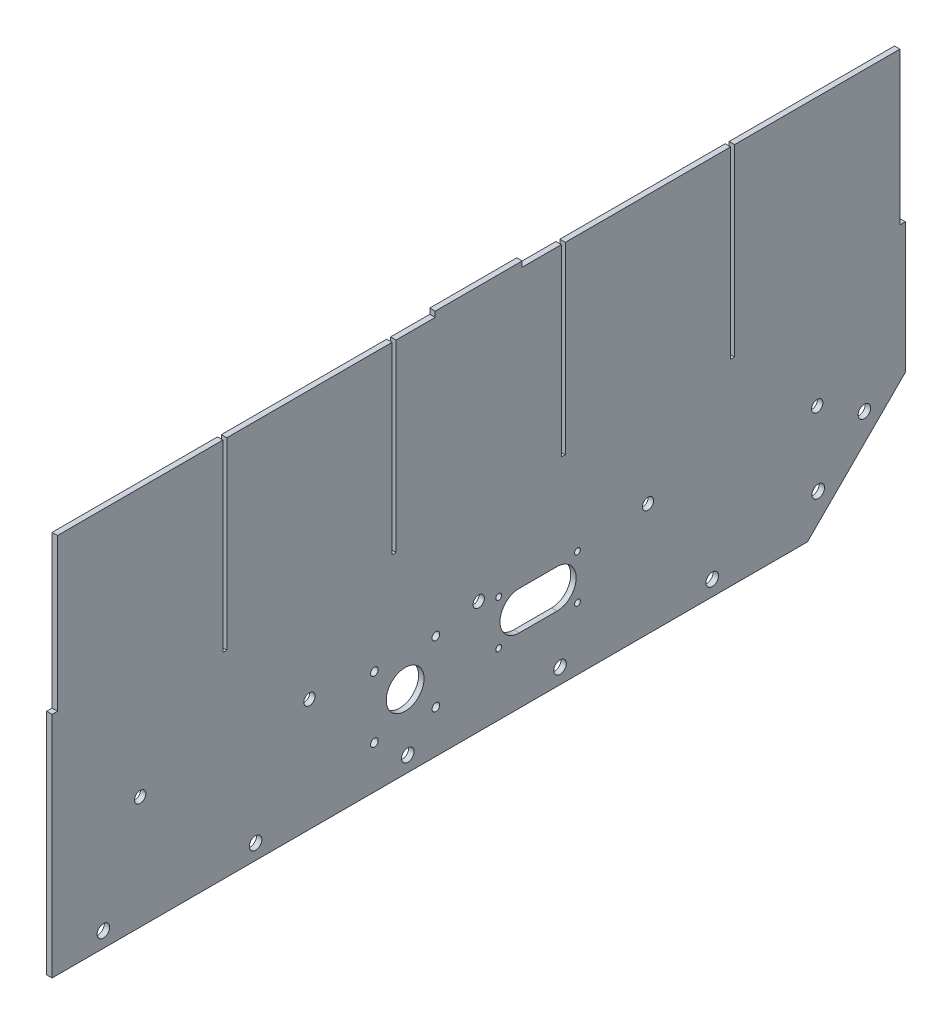
SolidWorks part; units mm, degrees
material "6061-T6 (SS)"
ref_plane "X-Y Datum" through (0, 0, 0) normal (0, 0, 1) x (1, 0, 0)
ref_plane "X-Z Datum" through (0, 0, 0) normal (0, 1, 0) x (1, 0, 0)
ref_plane "Y-Z Datum" through (0, 0, 0) normal (1, 0, 0) x (0, 0, -1)
sketch "Sketch1" plane through (0, 0, 0) normal (1, 0, 0) x (0, 0, -1)
  line L1 (-249.174, 82.55) -> (249.174, 82.55)
  line L2 (-249.174, 82.55) -> (-249.174, -82.55)
  line L3 (-249.174, -82.55) -> (249.174, -82.55)
  line L4 (249.174, 82.55) -> (249.174, -82.55)
  line L5 (-249.174, 82.55) -> (249.174, -82.55) construction
  line L6 (-249.174, -82.55) -> (249.174, 82.55) construction
  point P0 (0, 0)
  dimension "D1" = 165.1
  dimension "D2" = 498.348
extrude "Boss-Extrude1" add sketch "Sketch1" along normal mid plane 3.175
sketch "Sketch2" plane through (1.5875, 0, 0) normal (1, 0, 0) x (0, 0, -1)
  line L2 (249.174, -82.55) -> (192.024, -139.7)
  line L5 (-249.174, -82.55) -> (249.174, -82.55) construction
  line L6 (-249.174, -82.55) -> (249.174, -82.55)
  line L8 (192.024, -139.7) -> (-249.174, -139.7)
  line L9 (-249.174, -139.7) -> (-249.174, -82.55)
  line L11 (-249.174, 82.55) -> (-249.174, -82.55) construction
  line L12 (249.174, -82.55) -> (249.174, 82.55) construction
  line M10 (-249.174, -82.55) -> (249.174, -82.55)
  dimension "D1" = 45
  dimension "D5" = 57.15
extrude "Boss-Extrude2" add sketch "Sketch2" against normal blind 3.175 contours L2 M10 region at (1.5875, -110.5456, 13.9978)
sketch "Sketch3" plane through (-1.5875, 0, 0) normal (-1, 0, 0) x (0, 0, 1)
  line L0 (219.202, -139.7) -> (219.202, -130.81)
  line L1 (-192.024, -139.7) -> (249.174, -139.7) construction
  line L2 (219.202, -130.81) -> (249.174, -130.81)
  line L3 (249.174, 82.55) -> (249.174, -139.7) construction
  circle A0 centre (219.202, -130.81) radius 3.675
  dimension "D1" = 7.35
extrude "Cut-Extrude1" cut sketch "Sketch3" against normal through all contours L0 A0 L2 | L2 A0 L0 region at (-1.5875, -130.2901, 218.6821) region at (-1.5875, -132.3697, 220.7617)
pattern_linear "LPattern1" count 5 spacing 88.9 along (0, 0, -1) of "Cut-Extrude1"
sketch "Sketch4" plane through (-1.5875, 0, 0) normal (-1, 0, 0) x (0, 0, 1)
  line L0 (-206.3924, -125.3316) -> (-198.3102, -117.2494)
  line L1 (-249.174, -82.55) -> (-192.024, -139.7) construction
  line L2 (-192.024, -139.7) -> (-183.9418, -131.6178)
  line L3 (-183.9418, -131.6178) -> (-198.3102, -117.2494)
  circle A0 centre (-198.3102, -117.2494) radius 3.675
extrude "Cut-Extrude2" cut sketch "Sketch4" against normal through all and the other way through all contours L3 A0 L0 | L0 A0 L3 region at (-1.5875, -116.5141, -198.3102) region at (-1.5875, -119.4551, -198.3102)
pattern_linear "LPattern2" count 2 spacing 38.1 along (0, 0.7071, -0.7071) of "Cut-Extrude2"
sketch "Sketch5" plane through (1.5875, 0, 0) normal (1, 0, 0) x (0, 0, -1)
  line L1 (249.174, 82.55) -> (245.999, 82.55)
  line L2 (249.174, 82.55) -> (249.174, -6.35)
  line L3 (249.174, -6.35) -> (245.999, -6.35)
  line L4 (245.999, 82.55) -> (245.999, -6.35)
  line L5 (-249.174, 82.55) -> (-245.999, 82.55)
  line L6 (-249.174, 82.55) -> (-249.174, -6.35)
  line L7 (-249.174, -6.35) -> (-245.999, -6.35)
  line L8 (-245.999, 82.55) -> (-245.999, -6.35)
  dimension "D1" = 3.175
  dimension "D2" = 88.9
  dimension "D3" = 3.175
  dimension "D4" = 88.9
extrude "Cut-Extrude3" cut sketch "Sketch5" against normal through all
sketch "Sketch6" plane through (1.5875, 0, 0) normal (1, 0, 0) x (0, 0, -1)
  line L1 (149.4282, -24.892) -> (149.4282, 82.55) construction
  line L2 (122.174, 82.55) -> (249.174, 82.55)
  line L3 (149.4282, -24.892) -> (149.4282, 82.55)
  line L5 (149.4282, 82.55) -> (147.1422, 82.55)
  line L6 (149.4282, 82.55) -> (149.4282, -24.892)
  line L7 (149.4282, -24.892) -> (147.1422, -24.892)
  line L8 (147.1422, 82.55) -> (147.1422, -24.892)
  dimension "D1" = 2.286
  dimension "D2" = 107.442
extrude "Cut-Extrude4" cut sketch "Sketch6" against normal through all contours L2 L8 L7 L3 region at (1.5875, 28.829, -148.2852)
pattern_linear "LPattern3" count 4 spacing 98.8568 along (0, 0, 1) of "Cut-Extrude4"
sketch "Sketch8" plane through (1.5875, 0, 0) normal (1, 0, 0) x (0, 0, -1)
  line L0 (122.174, 85.725) -> (25.4, 85.725) construction
  line L1 (25.4, 82.55) -> (-25.4, 82.55)
  line L2 (25.4, 82.55) -> (25.4, 85.725)
  line L3 (25.4, 85.725) -> (-25.4, 85.725)
  line L4 (-25.4, 82.55) -> (-25.4, 85.725)
  line L5 (25.4, 82.55) -> (-25.4, 85.725) construction
  line L6 (25.4, 85.725) -> (-25.4, 82.55) construction
  point P0 (0, 84.1375)
  dimension "D1" = 3.175
  dimension "D2" = 50.8
extrude "Boss-Extrude3" add sketch "Sketch8" against normal blind 3.175
sketch "Sketch9" plane through (1.5875, 0, 0) normal (1, 0, 0) x (0, 0, -1)
  line L0 (-249.174, -6.35) -> (-249.174, -139.7) construction
  line L1 (192.024, -139.7) -> (-249.174, -139.7) construction
  circle A0 centre (-42.9768, -96.7994) radius 11.05
  dimension "D3" = 22.1
  dimension "D1" = 206.1972
  dimension "D2" = 42.9006
extrude "Cut-Extrude5" cut sketch "Sketch9" against normal through all
sketch "Sketch10" plane through (1.5875, 0, 0) normal (1, 0, 0) x (0, 0, -1)
  line L0 (192.024, -139.7) -> (-249.174, -139.7) construction
  circle A0 centre (0, -73.8124) radius 3
  dimension "D2" = 6
  dimension "D1" = 65.8876
hole_wizard "M6 Clearance Hole1" positions "Sketch11" profile "Sketch12" hole size "M6" standard "ANSI Metric" end condition through all
sketch "Sketch11" plane through (1.5875, 0, 0) normal (1, 0, 0) x (0, 0, -1)
  point P0 (0, -73.8124)
sketch "Sketch12" plane through (1.5875, -73.8124, 0) normal (0, 1, 0) x (0, 0, -1)
  line L0 (0, 0) -> (0, 3.175)
  line L1 (0, 3.175) -> (3.3, 3.175)
  line L2 (3.3, 3.175) -> (3.3, 0)
  line L5 (3.3, 0) -> (0, 0)
  line L11 (0, -6.35) -> (0, 107.95) construction
  dimension "Thru Hole Dia." = 6.6
  dimension "Thru Hole Depth" = 3.175
pattern_linear "LPattern4" count 3 spacing 98.8568 along (0, 0, 1) count 3 spacing 98.8568 along (0, 0, -1) of "M6 Clearance Hole1"
sketch "Sketch14" plane through (1.5875, 0, 0) normal (1, 0, 0) x (0, 0, -1)
  line L0 (192.024, -139.7) -> (-249.174, -139.7) construction
  line L1 (57.674, -103.315) -> (11.674, -103.315)
  line L2 (57.674, -103.315) -> (57.674, -77.315)
  line L3 (57.674, -77.315) -> (11.674, -77.315)
  line L4 (11.674, -103.315) -> (11.674, -77.315)
  line L5 (57.674, -103.315) -> (11.674, -77.315) construction
  line L6 (57.674, -77.315) -> (11.674, -103.315) construction
  line L7 (249.174, -82.55) -> (249.174, -6.35) construction
  line L8 (57.674, -90.315) -> (11.674, -90.315) construction
  line L9 (-25.0163, -114.7599) -> (-60.9373, -114.7599)
  line L10 (-25.0163, -114.7599) -> (-25.0163, -78.8389)
  line L11 (-25.0163, -78.8389) -> (-60.9373, -78.8389)
  line L12 (-60.9373, -114.7599) -> (-60.9373, -78.8389)
  line L13 (-25.0163, -114.7599) -> (-60.9373, -78.8389) construction
  line L14 (-25.0163, -78.8389) -> (-60.9373, -114.7599) construction
  line L15 (45.674, -90.315) -> (23.674, -90.315)
  line L16 (45.674, -101.565) -> (23.674, -101.565)
  line L17 (45.674, -79.065) -> (23.674, -79.065)
  arc A1 (45.674, -101.565) -> (45.674, -79.065) centre (45.674, -90.315) ccw
  arc A2 (23.674, -79.065) -> (23.674, -101.565) centre (23.674, -90.315) ccw
  point P0 (34.674, -90.315)
  point P10 (-42.9768, -96.7994)
  point P20 (34.674, -90.315)
  dimension "D7" = 11.25
  dimension "D1" = 46
  dimension "D2" = 26
  dimension "D3" = 36.385
  dimension "D4" = 191.5
  dimension "D5" = 35.921
  dimension "D6" = 22
hole_wizard "M3 Clearance Hole1" positions "Sketch15" profile "Sketch16" hole size "M3" standard "ANSI Metric" end condition through all
sketch "Sketch15" plane through (1.5875, 0, 0) normal (1, 0, 0) x (0, 0, -1)
  point P0 (11.674, -77.315)
  point P3 (11.674, -103.315)
  point P6 (57.674, -103.315)
  point P9 (57.674, -77.315)
sketch "Sketch16" plane through (1.5875, -77.315, -11.674) normal (0, 1, 0) x (0, 0, -1)
  line L0 (0, 0) -> (0, 3.175)
  line L1 (0, 3.175) -> (1.7, 3.175)
  line L2 (1.7, 3.175) -> (1.7, 0)
  line L5 (1.7, 0) -> (0, 0)
  line L11 (0, -6.35) -> (0, 107.95) construction
  dimension "Thru Hole Dia." = 3.4
  dimension "Thru Hole Depth" = 3.175
hole_wizard "M4 Clearance Hole1" positions "Sketch17" profile "Sketch18" hole size "M4" standard "ANSI Metric" end condition through all
sketch "Sketch17" plane through (1.5875, 0, 0) normal (1, 0, 0) x (0, 0, -1)
  point P0 (-25.0163, -78.8389)
  point P3 (-60.9373, -78.8389)
  point P6 (-60.9373, -114.7599)
  point P9 (-25.0163, -114.7599)
sketch "Sketch18" plane through (1.5875, -78.8389, 25.0163) normal (0, 1, 0) x (0, 0, -1)
  line L0 (0, 0) -> (0, 3.175)
  line L1 (0, 3.175) -> (2.25, 3.175)
  line L2 (2.25, 3.175) -> (2.25, 0)
  line L5 (2.25, 0) -> (0, 0)
  line L11 (0, -6.35) -> (0, 107.95) construction
  dimension "Thru Hole Dia." = 4.5
  dimension "Thru Hole Depth" = 3.175
extrude "Cut-Extrude6" cut sketch "Sketch14" against normal through all contours L17 A2 L16 A1 region at (1.5875, -101.0664, -34.674)
